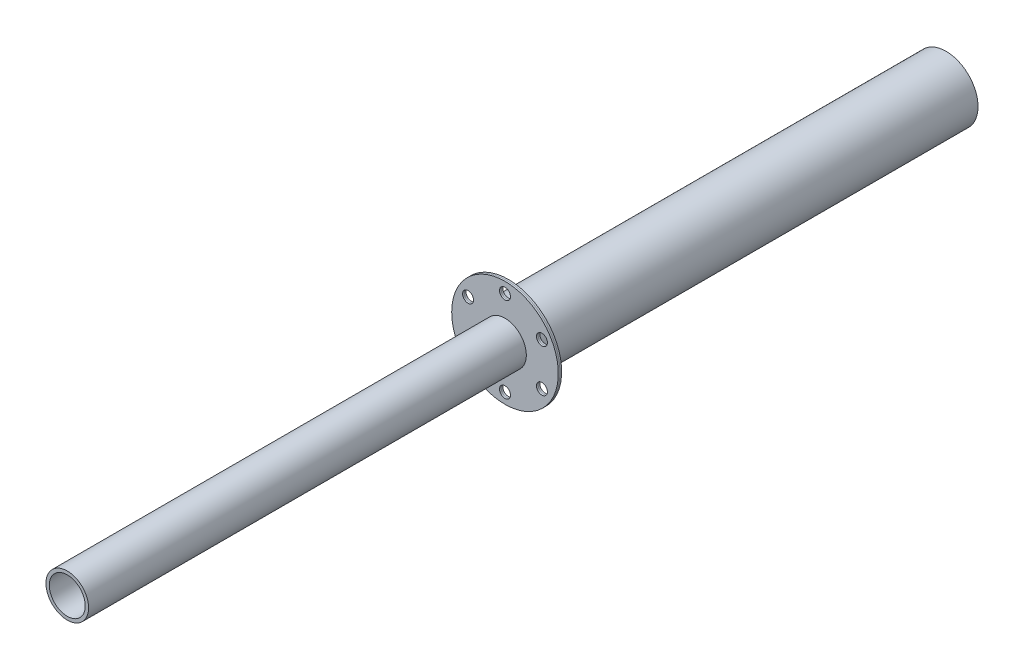
SolidWorks part; units mm, degrees
material "ASTM A36 Steel"
ref_plane "Front Plane" through (0, 0, 0) normal (0, 0, 1) x (1, 0, 0)
ref_plane "Top Plane" through (0, 0, 0) normal (0, 1, 0) x (1, 0, 0)
ref_plane "Right Plane" through (0, 0, 0) normal (1, 0, 0) x (0, 0, -1)
sketch "Sketch1" plane through (0, 0, 0) normal (0, 0, 1) x (1, 0, 0)
  circle A0 centre (0, 0) radius 12.7
  circle A1 centre (0, 0) radius 10.7
  dimension "D1" = 25.4
  dimension "D2" = 2
extrude "Boss-ExtrudeInnerTube" add sketch "Sketch1" against normal blind 261.7
sketch "Sketch2" plane through (0, 0, -261.7) normal (0, 0, -1) x (-1, 0, 0)
  line L0 (0, 0) -> (0, 25.4) construction
  line L1 (21.997, 12.7) -> (0, 25.4) construction
  line L2 (0, 25.4) -> (-21.997, 12.7) construction
  line L3 (-21.997, 12.7) -> (-21.997, -12.7) construction
  line L4 (-21.997, -12.7) -> (0, -25.4) construction
  line L5 (0, -25.4) -> (21.997, -12.7) construction
  line L6 (21.997, -12.7) -> (21.997, 12.7) construction
  line L7 (0, 0) -> (10.9985, 19.05) construction
  circle A0 centre (0, 0) radius 21.997 construction
  circle A1 centre (0, 25.4) radius 6.5 construction
  circle A2 centre (0, 0) radius 12.7
  circle A3 centre (0, 0) radius 25.4 construction
  circle A4 centre (0, 0) radius 31.75
  circle A5 centre (0, 0) radius 12.7 construction
  circle A7 centre (0, 25.4) radius 3.2639
  circle A8 centre (21.997, 12.7) radius 3.2639
  circle A9 centre (21.997, -12.7) radius 3.2639
  circle A10 centre (0, -25.4) radius 3.2639
  circle A11 centre (-21.997, -12.7) radius 3.2639
  circle A12 centre (-21.997, 12.7) radius 3.2639
  circle A13 centre (0, 0) radius 19.05 construction
  dimension "D1" = 13
  dimension "D2" = 50.8
  dimension "D3" = 6.5278
  dimension "D5" = 63.5
  dimension "D6" = 38.1
  dimension "D4" = 6
extrude "Boss-ExtrudeFrontFlange" add sketch "Sketch2" against normal blind 1 separate body
sketch "Sketch3" plane through (0, 0, -261.7) normal (0, 0, -1) x (-1, 0, 0)
  circle A0 centre (0, 0) radius 19.05
  circle A1 centre (0, 0) radius 17.85
  dimension "D1" = 38.1
  dimension "D2" = 1.2
extrude "Boss-ExtrudeOuterTube" add sketch "Sketch3" along normal blind 261.7 separate body
sketch "Sketch4" plane through (0, 0, -261.7) normal (0, 0, -1) x (-1, 0, 0)
  circle A0 centre (0, 0) radius 31.75 construction
  circle A1 centre (-21.997, 12.7) radius 3.2639 construction
  circle A2 centre (0, 25.4) radius 3.2639 construction
  circle A3 centre (-21.997, -12.7) radius 3.2639 construction
  circle A4 centre (21.997, 12.7) radius 3.2639 construction
  circle A5 centre (21.997, -12.7) radius 3.2639 construction
  circle A6 centre (0, -25.4) radius 3.2639 construction
  circle A7 centre (0, 0) radius 31.75
  circle A8 centre (-21.997, 12.7) radius 3.2639
  circle A9 centre (0, 25.4) radius 3.2639
  circle A10 centre (-21.997, -12.7) radius 3.2639
  circle A11 centre (21.997, 12.7) radius 3.2639
  circle A12 centre (21.997, -12.7) radius 3.2639
  circle A13 centre (0, -25.4) radius 3.2639
  circle A14 centre (0, 0) radius 19.05 construction
  circle A15 centre (0, 0) radius 19.05
extrude "Boss-ExtrudeRearFlange" add sketch "Sketch4" along normal blind 1 separate body
sketch "Sketch5" [suppressed] plane through (0, 0, 0) normal (1, 0, 0) x (0, 0, -1)
  line L1 (290, 31.75) -> (290, -31.75) construction
  line L2 (271.4958, 41.9152) -> (308.5042, 41.9152)
  line L3 (271.4958, 41.9152) -> (271.4958, -41.9152)
  line L4 (271.4958, -41.9152) -> (308.5042, -41.9152)
  line L5 (308.5042, 41.9152) -> (308.5042, -41.9152)
  line L6 (271.4958, 41.9152) -> (308.5042, -41.9152) construction
  line L7 (271.4958, -41.9152) -> (308.5042, 41.9152) construction
  point P2 (290, 0)
extrude "Cut-ExtrudeSmaller4FEA" [suppressed] cut sketch "Sketch5" against normal through all and the other way through all flip side to cut
sketch "Sketch6" [suppressed] plane through (0, 0, -291) normal (0, 0, 1) x (1, 0, 0)
  circle A0 centre (0, 25.4) radius 3.2639 construction
  circle A1 centre (21.997, 12.7) radius 3.2639 construction
  circle A2 centre (21.997, -12.7) radius 3.2639 construction
  circle A3 centre (0, -25.4) radius 3.2639 construction
  circle A4 centre (-21.997, 12.7) radius 3.2639 construction
  circle A5 centre (-21.997, -12.7) radius 3.2639 construction
  circle A6 centre (0, 25.4) radius 3.2639
  circle A7 centre (21.997, 12.7) radius 3.2639
  circle A8 centre (21.997, -12.7) radius 3.2639
  circle A9 centre (0, -25.4) radius 3.2639
  circle A10 centre (-21.997, 12.7) radius 3.2639
  circle A11 centre (-21.997, -12.7) radius 3.2639
extrude "Boss-ExtrudeBolts4FEA" [suppressed] add sketch "Sketch6" along normal blind 12.7 and the other way blind 12.7 separate body
combine bodies "Combine1" [suppressed] operation type add bodies to combine 102 105
combine bodies "Combine2" [suppressed] operation type add bodies to combine 106 104
combine bodies "Combine3" [suppressed] operation type add bodies to combine 101 102
fillet "Fillet1" [suppressed] radius 2
delete or keep bodies "Body-DeleteAllButInnerTube" [suppressed] type delete bodies bodies 102
delete or keep bodies "Body-Delete2AllButInnerFlange" [suppressed] type delete bodies bodies 101
delete or keep bodies "Body-DeleteAllButOuter" [suppressed] type delete bodies bodies 101 102
combine bodies "CombineOuter" [suppressed] operation type add bodies to combine 104 103
fillet "FilletOuter" [suppressed] radius 2
delete or keep bodies "Body-DeleteAllButOuterTube" [suppressed] type delete bodies bodies 104
delete or keep bodies "Body-DeleteAllButOuterFlange" [suppressed] type delete bodies bodies 103
sketch3d "3DSketch1"
  line L0 (0, 0, 0) -> (0, 0, -523.4) construction
  line L1 (0, 0, -523.4) -> (0, 0, -261.7) construction
  line L2 (0, 0, -523.4) -> (0, 0, -261.7) construction
